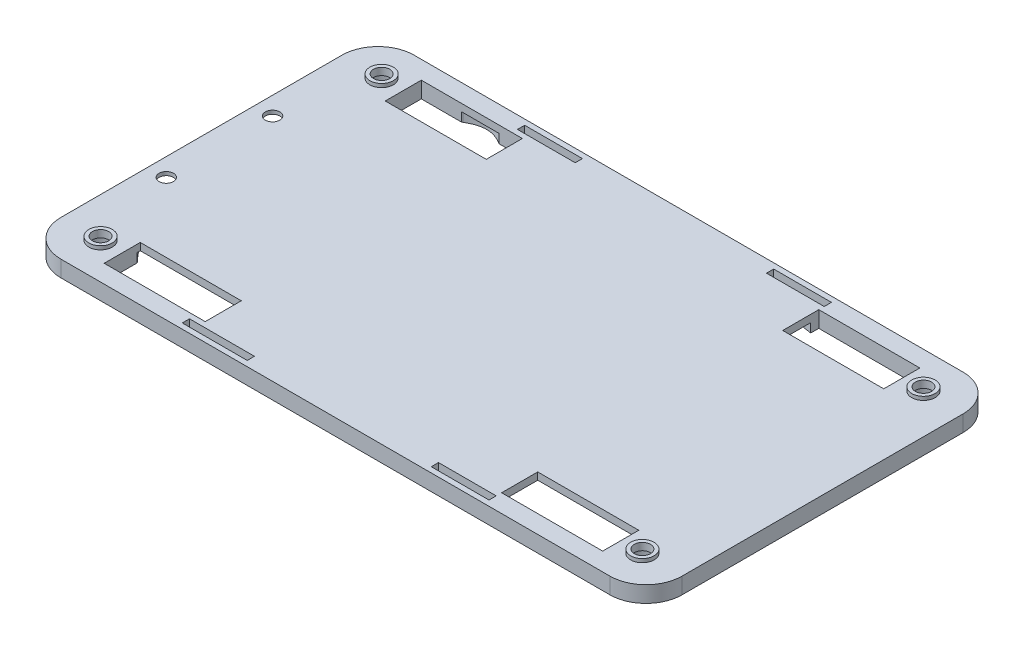
SolidWorks part; units mm, degrees
ref_plane "Front Plane" through (0, 0, 0) normal (0, 0, 1) x (1, 0, 0)
ref_plane "Top Plane" through (0, 0, 0) normal (0, 1, 0) x (1, 0, 0)
ref_plane "Right Plane" through (0, 0, 0) normal (1, 0, 0) x (0, 0, -1)
sketch "Sketch1" plane through (0, 0, 0) normal (0, 1, 0) x (1, 0, 0)
  line L1 (-78.1571, 35.933) -> (-78.1571, -14.1122)
  line L2 (78.9797, 0.0343) -> (-78.1571, 0.0343) construction
  line L3 (-77.1571, 35.7646) -> (-77.1571, -14.1122)
  line L4 (78.9797, -0.9657) -> (-78.1571, -0.9657)
  arc A1 (37.8695, -35.2975) -> (39.5975, -35.2134) centre (38.2635, -25.6055) ccw
  arc A2 (37.9263, -34.299) -> (39.4753, -34.2207) centre (38.2635, -25.6055) ccw
  spline S0 degree 1 poles (-77.1571, -14.1122) (-56.919, -31.9168) knots 0 0 1 1 construction
  spline S1 degree 1 poles (-56.919, -31.9168) (37.9263, -34.299) knots 0 0 1 1 construction
  spline S2 degree 1 poles (39.4753, -34.2207) (77.9849, 0.1477) knots 0 0 1 1 construction
  spline S3 degree 1 poles (77.9849, 0.1477) (25.0602, 52.8732) knots 0 0 1 1 construction
  spline S4 degree 1 poles (25.0602, 52.8732) (-5.6593, 44.1904) knots 0 0 1 1 construction
  spline S5 degree 1 poles (-5.6593, 44.1904) (-43.9853, 50.6886) knots 0 0 1 1 construction
  spline S6 degree 1 poles (-43.9853, 50.6886) (-59.7702, 54.7238) knots 0 0 1 1 construction
  spline S7 degree 1 poles (-59.7702, 54.7238) (-74.5158, 41.0521) knots 0 0 1 1 construction
  spline S8 degree 1 poles (-74.5158, 41.0521) (-77.1571, 35.7646) knots 0 0 1 1 construction
  spline S9 degree 3 poles (-77.1571, -14.1122) (-77.1565, -14.3701) (-77.1092, -14.8732) (-76.8359, -15.9559) (-76.1879, -17.5008) (-75.044, -19.4183) (-73.152, -22.0092) (-70.3495, -25.0822) (-66.8736, -28.0972) (-63.6864, -30.2141) (-61.0019, -31.4062) (-58.8274, -31.848) (-57.5718, -31.8794) (-56.919, -31.9168) knots 0.000484 0.000484 0.000484 0.000484 0.031521 0.062558 0.124632 0.186706 0.248781 0.372929 0.497077 0.621225 0.745373 0.869521 0.993669 0.993669 0.993669 0.993669
  spline S10 degree 3 poles (-56.919, -31.9168) (-56.6769, -31.8873) (-56.2021, -31.8274) (-55.1791, -31.687) (-53.8294, -31.4877) (-52.0759, -31.2184) (-49.5744, -30.8354) (-46.1465, -30.3372) (-41.5825, -29.7813) (-36.5976, -29.3261) (-29.4274, -28.913) (-19.5571, -28.8468) (-6.4839, -29.5875) (5.2448, -30.7865) (15.023, -31.9295) (22.521, -32.809) (30.1538, -33.642) (35.3408, -34.1075) (37.9263, -34.299) knots 0.000538 0.000538 0.000538 0.000538 0.016152 0.031766 0.062993 0.094221 0.125449 0.187904 0.250359 0.312815 0.37527 0.50018 0.625091 0.750001 0.812457 0.874912 0.937367 0.999822 0.999822 0.999822 0.999822
  spline S11 degree 3 poles (39.4753, -34.2207) (41.0079, -34.0574) (44.09, -33.7147) (50.0835, -32.8429) (57.0969, -31.1859) (64.2184, -27.8839) (69.7763, -23.1857) (73.0497, -18.2789) (74.9177, -14.0269) (75.9805, -10.7732) (76.7509, -7.5724) (77.1995, -5.064) (77.4798, -3.2279) (77.6607, -1.9649) (77.8261, -0.8108) (77.9301, -0.1834) (77.9849, 0.1477) knots -0.000309 -0.000309 -0.000309 -0.000309 0.063093 0.126495 0.253299 0.380104 0.506908 0.633712 0.697114 0.760516 0.823918 0.88732 0.919021 0.950722 0.982423 1.014124 1.014124 1.014124 1.014124
  spline S12 degree 3 poles (77.9849, 0.1477) (78.0286, 1.2633) (78.0637, 3.5224) (77.9426, 6.757) (77.6596, 9.9047) (77.0733, 13.9671) (75.9626, 18.7836) (73.4433, 25.9357) (69.0206, 33.8098) (62.0495, 41.4932) (53.7895, 47.3444) (44.6121, 51.2947) (34.9036, 53.2804) (28.3113, 53.2357) (25.0602, 52.8732) knots 0.000169 0.000169 0.000169 0.000169 0.031414 0.062658 0.093902 0.125147 0.187635 0.250124 0.375101 0.500079 0.625056 0.750034 0.875011 0.999988 0.999988 0.999988 0.999988
  spline S13 degree 3 poles (25.0602, 52.8732) (19.8954, 51.6294) (12.3224, 49.1317) (2.1607, 45.9713) (-3.0371, 44.6913) (-5.6593, 44.1904) knots 0.000659 0.000659 0.000659 0.000659 0.498067 0.746772 0.995476 0.995476 0.995476 0.995476
  spline S14 degree 3 poles (-5.6593, 44.1904) (-6.6879, 44.0461) (-8.7287, 43.7719) (-12.9633, 43.2668) (-18.1826, 42.7952) (-23.9015, 42.6322) (-28.8306, 42.9899) (-32.9666, 43.9514) (-35.9177, 45.2914) (-38.1959, 46.6779) (-39.9392, 47.8658) (-41.507, 48.9798) (-42.8638, 49.9292) (-43.6163, 50.4405) (-43.9853, 50.6886) knots -0.000196 -0.000196 -0.000196 -0.000196 0.062587 0.12537 0.250936 0.376501 0.502067 0.627632 0.753198 0.815981 0.878764 0.941546 0.972938 1.004329 1.004329 1.004329 1.004329
  spline S15 degree 3 poles (-43.9853, 50.6886) (-44.2445, 50.8673) (-44.7682, 51.2325) (-45.7507, 51.9331) (-46.8912, 52.7591) (-48.146, 53.6496) (-49.6971, 54.6811) (-51.4608, 55.6487) (-53.4077, 56.2593) (-55.2517, 56.3574) (-56.711, 56.0808) (-57.7948, 55.7138) (-58.5465, 55.3915) (-59.2299, 55.0428) (-59.5837, 54.8359) (-59.7702, 54.7238) knots -0.002497 -0.002497 -0.002497 -0.002497 0.029066 0.060629 0.123754 0.18688 0.250006 0.376257 0.502509 0.62876 0.755012 0.818137 0.881263 0.944389 1.007515 1.007515 1.007515 1.007515
  spline S16 degree 3 poles (-78.1571, -14.1122) (-78.1559, -14.7524) (-77.9173, -15.9777) (-77.0678, -17.9828) (-75.8538, -20.0098) (-73.8827, -22.6985) (-70.9901, -25.8584) (-67.4096, -28.9504) (-64.0991, -31.1349) (-61.2379, -32.3904) (-59.243, -32.7789) (-57.8421, -32.8756) (-57.2118, -32.9007) (-56.8882, -32.9203) knots 0.000409 0.000409 0.000409 0.000409 0.062843 0.125276 0.18771 0.250143 0.375011 0.499878 0.624745 0.749612 0.874479 0.936913 0.999346 0.999346 0.999346 0.999346
  spline S17 degree 3 poles (-56.8882, -32.9203) (-56.6427, -32.8908) (-56.1603, -32.8306) (-55.1309, -32.6904) (-53.7754, -32.491) (-52.0233, -32.2221) (-49.5292, -31.8398) (-46.1189, -31.3427) (-41.5829, -30.7872) (-36.6286, -30.3313) (-29.4997, -29.9158) (-19.6749, -29.8441) (-6.6369, -30.5782) (5.0856, -31.7749) (14.8757, -32.919) (22.3927, -33.8009) (30.0532, -34.6371) (35.2704, -35.1052) (37.8695, -35.2975) knots -0.001373 -0.001373 -0.001373 -0.001373 0.014273 0.029919 0.06121 0.092502 0.123794 0.186377 0.24896 0.311543 0.374127 0.499293 0.62446 0.749626 0.81221 0.874793 0.937376 0.99996 0.99996 0.99996 0.99996
  spline S18 degree 3 poles (39.5975, -35.2134) (41.1398, -35.049) (44.2356, -34.7045) (50.3018, -33.8209) (57.4502, -32.1301) (64.7991, -28.7164) (70.5782, -23.8111) (73.9656, -18.7006) (75.8832, -14.3057) (76.9672, -10.962) (77.7479, -7.6914) (78.1997, -5.145) (78.4804, -3.2966) (78.6613, -2.0308) (78.824, -0.9009) (78.9276, -0.2806) (78.9816, 0.0458) knots -0.000086 -0.000086 -0.000086 -0.000086 0.063428 0.126941 0.253967 0.380993 0.50802 0.635046 0.698559 0.762072 0.825585 0.889098 0.920855 0.952612 0.984368 1.016125 1.016125 1.016125 1.016125
  spline S19 degree 3 poles (78.9816, 0.0458) (79.0271, 1.1797) (79.0647, 3.4739) (78.9444, 6.7697) (78.6587, 9.9749) (78.0642, 14.1169) (76.9341, 19.0326) (74.3646, 26.3398) (69.8439, 34.3944) (62.712, 42.2543) (54.2626, 48.2351) (44.8799, 52.2671) (34.9529, 54.2886) (28.2109, 54.2351) (24.8869, 53.8601) knots -0.000407 -0.000407 -0.000407 -0.000407 0.03088 0.062166 0.093453 0.12474 0.187314 0.249888 0.375035 0.500183 0.62533 0.750478 0.875625 1.000773 1.000773 1.000773 1.000773
  spline S20 degree 3 poles (24.8869, 53.8601) (22.2839, 53.2349) (17.1223, 51.77) (6.9788, 48.4835) (-0.6206, 46.1711) (-5.8226, 45.1772) knots -0.001281 -0.001281 -0.001281 -0.001281 0.247714 0.49671 0.9947 0.9947 0.9947 0.9947
  spline S21 degree 3 poles (-5.8226, 45.1772) (-6.8463, 45.0337) (-8.8779, 44.761) (-13.0882, 44.2593) (-18.2643, 43.7927) (-23.9018, 43.6338) (-28.7026, 43.9859) (-32.6523, 44.9085) (-35.4477, 46.177) (-37.6484, 47.5152) (-39.3619, 48.6824) (-40.9248, 49.793) (-42.292, 50.7496) (-43.0505, 51.2651) (-43.4225, 51.5151) knots 0.000305 0.000305 0.000305 0.000305 0.063048 0.125791 0.251276 0.376761 0.502247 0.627732 0.753218 0.815961 0.878703 0.941446 0.972817 1.004189 1.004189 1.004189 1.004189
  spline S22 degree 3 poles (-43.4225, 51.5151) (-43.6786, 51.6918) (-44.1958, 52.0526) (-45.1684, 52.7462) (-46.308, 53.5714) (-47.577, 54.4721) (-49.1727, 55.5335) (-51.0441, 56.5648) (-53.2147, 57.2519) (-55.3195, 57.3652) (-56.9568, 57.0533) (-58.1477, 56.6506) (-58.9689, 56.2985) (-59.5708, 55.992) (-60.0059, 55.7483) (-60.1862, 55.6406) (-60.2803, 55.5839) knots -0.002294 -0.002294 -0.002294 -0.002294 0.029245 0.060783 0.12386 0.186936 0.250013 0.376167 0.50232 0.628473 0.754627 0.817704 0.88078 0.943857 0.975396 1.006934 1.006934 1.006934 1.006934
  spline S23 degree 3 poles (-60.2803, 55.5839) (-60.715, 55.3297) (-61.582, 54.801) (-63.2222, 53.7187) (-65.9105, 51.7373) (-69.2431, 48.741) (-72.0244, 45.6929) (-73.7392, 43.6279) (-74.6657, 42.4756) (-75.1049, 41.9202) (-75.3265, 41.639) knots 0.000427 0.000427 0.000427 0.000427 0.063268 0.126109 0.251792 0.503158 0.754524 0.880206 0.943048 1.005889 1.005889 1.005889 1.005889
  spline S24 degree 3 poles (-59.7702, 54.7238) (-60.1936, 54.4761) (-61.0386, 53.9612) (-62.6368, 52.9072) (-65.2587, 50.9763) (-68.5171, 48.0498) (-71.2443, 45.0657) (-73.1899, 42.7247) (-74.0698, 41.6179) (-74.5158, 41.0521) knots 0.000174 0.000174 0.000174 0.000174 0.062881 0.125589 0.251004 0.501833 0.752662 0.878077 1.003492 1.003492 1.003492 1.003492
  spline S25 degree 3 poles (-74.5158, 41.0521) (-75.0658, 40.2217) (-76.0765, 38.4779) (-76.8336, 36.6875) (-77.1571, 35.7646) knots 0.499549 0.499549 0.499549 0.499549 0.499766 0.499983 0.499983 0.499983 0.499983
  spline S26 degree 3 poles (-75.3265, 41.639) (-75.92, 40.746) (-77.0064, 38.8701) (-77.815, 36.9314) (-78.1571, 35.933) knots 0.499546 0.499546 0.499546 0.499546 0.49977 0.499995 0.499995 0.499995 0.499995
  point P0 (0.4631, 0.0343)
  dimension "D1" = 1
sketch "Sketch6" plane through (0, 0, 0) normal (0, 1, 0) x (1, 0, 0)
  line L0 (-78.1571, 35.933) -> (-78.1571, -14.1122) construction
  line L1 (73.9816, 59.5839) -> (-78.1571, 59.5839)
  line L2 (83.9816, 49.5839) -> (83.9816, -28.2975)
  line L3 (73.9816, -38.2975) -> (-78.1571, -38.2975)
  line L4 (-88.1571, 49.5839) -> (-88.1571, -28.2975)
  arc A0 (-78.1571, -38.2975) -> (-88.1571, -28.2975) centre (-78.1571, -28.2975) cw
  arc A1 (-88.1571, 49.5839) -> (-78.1571, 59.5839) centre (-78.1571, 49.5839) cw
  arc A2 (73.9816, 59.5839) -> (83.9816, 49.5839) centre (73.9816, 49.5839) cw
  arc A3 (83.9816, -28.2975) -> (73.9816, -38.2975) centre (73.9816, -28.2975) cw
  dimension "D5" = 10
  dimension "D1" = 5
  dimension "D2" = 10
  dimension "D3" = 3
  dimension "D4" = 4
extrude "Boss-Extrude2" add sketch "Sketch6" along normal blind 5.5
extrude "Cut-Extrude1" cut sketch "Sketch1" along normal blind 2.5 contours A2 S11 L4 L3 S9 S10 | S24 S25 L3 L4 S11 S12 S13 S14 S15 region at (0.1139, 0, 15.5782) region at (-2.2602, 0, -23.2786)
sketch "Sketch7" plane through (0, 0, 0) normal (0, -1, 0) x (1, 0, 0)
  line L1 (-76.2189, 14.1122) -> (-91.3452, 14.1122)
  line L2 (-76.2189, 14.1122) -> (-76.2189, -35.933)
  line L3 (-76.2189, -35.933) -> (-91.3452, -35.933)
  line L4 (-91.3452, 14.1122) -> (-91.3452, -35.933)
extrude "Cut-Extrude2" cut sketch "Sketch7" against normal up to surface (2.5 mm away) contours L2 L1 L4 L3 up to face at (-19.4492, 2.5, -12.7234)
sketch "Sketch8" plane through (0, 5.5, 0) normal (0, 1, 0) x (1, 0, 0)
  line L0 (83.9816, 10.6432) -> (-88.1571, 10.6432) construction
  line L1 (83.9816, -28.2975) -> (83.9816, 49.5839) construction
  line L2 (-88.1571, 49.5839) -> (-88.1571, -28.2975) construction
  line L3 (-2.0877, 59.5839) -> (-2.0877, -38.2975) construction
  line L4 (73.9816, 59.5839) -> (-78.1571, 59.5839) construction
  line L5 (-78.1571, -38.2975) -> (73.9816, -38.2975) construction
  line L7 (78.9816, 54.5839) -> (38.9816, 54.5839)
  line L8 (78.9816, 54.5839) -> (78.9816, 44.5839)
  line L9 (78.9816, 44.5839) -> (38.9816, 44.5839)
  line L10 (38.9816, 54.5839) -> (38.9816, 44.5839)
  line L22 (38.9816, 49.5839) -> (78.9816, 49.5839) construction
  line L23 (66.9816, 54.5839) -> (66.9816, 44.5839)
  circle A1 centre (72.9816, 49.5839) radius 3.5
  dimension "D6" = 7
  dimension "D1" = 10
  dimension "D2" = 40
  dimension "D3" = 5
  dimension "D4" = 5
  dimension "D5" = 6
  dimension "D7" = 6
sketch "Sketch9" plane through (0, 0, 0) normal (0, -1, 0) x (1, 0, 0)
  circle A0 centre (72.9816, -49.5839) radius 4.5
  dimension "D1" = 9
extrude "Cut-Extrude5" cut sketch "Sketch9" against normal blind 3.5
sketch "Sketch10" plane through (0, 3.5, 0) normal (0, -1, 0) x (1, 0, 0)
  circle A0 centre (72.9816, -49.5839) radius 2.25
  dimension "D1" = 4.5
extrude "Cut-Extrude6" cut sketch "Sketch10" against normal blind 21
extrude "Cut-Extrude8" cut sketch "Sketch8" against normal blind 42 contours L23 L7 L10 L9 region at (52.9816, 5.5, -49.5839)
extrude "Cut-Extrude9" cut sketch "Sketch8<3>" against normal blind 1 contours L7 L23 L9 L8 A1 region at (78.8254, 5.5, -49.5839)
sketch "Sketch8<3>" plane through (0, 5.5, 0) normal (0, 1, 0) x (1, 0, 0) same geometry as "Sketch8"
sketch "Sketch12" plane through (0, 5.5, 0) normal (0, 1, 0) x (1, 0, 0)
  line L0 (-88.1571, 10.6432) -> (83.9816, 10.6432) construction
  line L1 (-88.1571, 49.5839) -> (-88.1571, -28.2975) construction
  line L2 (83.9816, -28.2975) -> (83.9816, 49.5839) construction
  line L3 (-2.0877, 59.5839) -> (-2.0877, -36.8461) construction
  line L4 (73.9816, 59.5839) -> (-78.1571, 59.5839) construction
ref_plane "Plane1" through (0, 0, -10.6432) normal (0, 0, 1) x (1, 0, 0)
ref_plane "Plane2" through (-2.0877, 0, 0) normal (-1, 0, 0) x (0, 0, 1)
mirror "Mirror1" about plane through (0, 0, -10.6432) normal (0, 0, 1) of "Cut-Extrude5", "Cut-Extrude6", "Cut-Extrude8", "Cut-Extrude9"
mirror "Mirror2" about plane through (-2.0877, 0, 0) normal (-1, 0, 0) of "Mirror1", "Cut-Extrude9", "Cut-Extrude8", "Cut-Extrude6", "Cut-Extrude5"
sketch "Sketch13" plane through (0, 5.5, 0) normal (0, 1, 0) x (1, 0, 0)
  line L0 (-83.1571, 44.5839) -> (-43.1571, 44.5839) construction
  line L1 (58.9816, 39.5839) -> (-63.1571, 39.5839)
  line L2 (58.9816, 39.5839) -> (58.9816, -18.2975)
  line L3 (58.9816, -18.2975) -> (-63.1571, -18.2975)
  line L4 (-63.1571, 39.5839) -> (-63.1571, -18.2975)
  line L5 (58.9816, 39.5839) -> (-63.1571, -18.2975) construction
  line L6 (58.9816, -18.2975) -> (-63.1571, 39.5839) construction
  line L7 (-83.1571, -23.2975) -> (-43.1571, -23.2975) construction
  line L8 (83.9816, -28.2975) -> (83.9816, 49.5839) construction
  line L9 (-88.1571, 49.5839) -> (-88.1571, -28.2975) construction
  point P0 (-2.0877, 10.6432)
  dimension "D1" = 5
  dimension "D2" = 5
  dimension "D3" = 25
  dimension "D4" = 25
extrude "Cut-Extrude10" cut sketch "Sketch13" against normal blind 1
sketch "Sketch16" plane through (0, 0, 0) normal (0, -1, 0) x (1, 0, 0)
  line L0 (78.9816, -0.5458) -> (78.9816, -79.1994) construction
  line L1 (22.9816, -56.0839) -> (-37.6427, -56.0839) construction
  line L2 (73.9816, -59.5839) -> (-78.1571, -59.5839) construction
  line L3 (38.9816, -54.3238) -> (38.9816, 38.2975) construction
  line L4 (38.9816, -59.5839) -> (38.9816, -54.3238) construction
  line L5 (38.9816, -56.0839) -> (22.9816, -56.0839)
  line L6 (38.9816, -56.0839) -> (38.9816, -58.0839)
  line L7 (38.9816, -58.0839) -> (22.9816, -58.0839)
  line L8 (22.9816, -56.0839) -> (22.9816, -58.0839)
  line L9 (-78.1571, 38.2975) -> (73.9816, 38.2975) construction
  line L10 (22.9816, -56.0839) -> (22.9816, 38.2975) construction
  line L12 (38.9816, 36.7975) -> (22.9816, 36.7975)
  line L13 (38.9816, 36.7975) -> (38.9816, 34.7975)
  line L14 (38.9816, 34.7975) -> (22.9816, 34.7975)
  line L15 (22.9816, 36.7975) -> (22.9816, 34.7975)
  line L16 (22.9816, 34.7975) -> (-46.0184, 34.7975) construction
  line L17 (-30.0184, -56.0839) -> (-46.0184, -56.0839)
  line L18 (-30.0184, -56.0839) -> (-30.0184, -58.0839)
  line L19 (-30.0184, -58.0839) -> (-46.0184, -58.0839)
  line L20 (-46.0184, -56.0839) -> (-46.0184, -58.0839)
  line L22 (-28.0184, 34.7975) -> (-46.0184, 34.7975)
  line L23 (-28.0184, 34.7975) -> (-28.0184, 36.7975)
  line L24 (-28.0184, 36.7975) -> (-46.0184, 36.7975)
  line L25 (-46.0184, 34.7975) -> (-46.0184, 36.7975)
  dimension "D1" = 40
  dimension "D2" = 16
  dimension "D3" = 1.5
  dimension "D4" = 2
  dimension "D5" = 2
  dimension "D6" = 1.5
  dimension "D7" = 125
  dimension "D8" = 16
  dimension "D9" = 2
  dimension "D10" = 18
  dimension "D11" = 2
extrude "Cut-Extrude12" cut sketch "Sketch16" against normal blind 57
sketch "Sketch17" plane through (0, 4.5, 0) normal (0, 1, 0) x (1, 0, 0)
  line L1 (-99.5963, 69.0247) -> (98.4238, 69.0247)
  line L2 (-99.5963, 69.0247) -> (-99.5963, -53.2143)
  line L3 (-99.5963, -53.2143) -> (98.4238, -53.2143)
  line L4 (98.4238, 69.0247) -> (98.4238, -53.2143)
extrude "Cut-Extrude14" cut sketch "Sketch17" along normal blind 48.5
sketch "Sketch23" plane through (0, 2.5, 0) normal (0, -1, 0) x (1, 0, 0)
  line L0 (-88.1571, -10.9104) -> (-64.7808, -10.9104) construction
  line L1 (-88.1571, -35.933) -> (-88.1571, 14.1122) construction
  circle A0 centre (-83.1571, 4.0896) radius 2
  circle A1 centre (-83.1571, 4.0896) radius 4.25
  dimension "D1" = 4
  dimension "D4" = 8.5
  dimension "D2" = 15
  dimension "D3" = 5
extrude "Cut-Extrude15" cut sketch "Sketch23" against normal blind 48.5 contours A0
extrude "Cut-Extrude16" cut sketch "Sketch23<3>" against normal blind 1
sketch "Sketch23<3>" plane through (0, 2.5, 0) normal (0, -1, 0) x (1, 0, 0) same geometry as "Sketch23"
mirror "Mirror4" about plane through (0, 0, -10.6432) normal (0, 0, 1) of "Cut-Extrude16", "Cut-Extrude15"
sketch "Sketch24" plane through (0, 4.5, 0) normal (0, 1, 0) x (1, 0, 0)
  circle A0 centre (-77.1571, 49.5839) radius 3.25
  circle A1 centre (-77.1571, 49.5839) radius 2.25
  circle A2 centre (72.9816, 49.5839) radius 2.25
  circle A3 centre (72.9816, 49.5839) radius 3.25
  circle A4 centre (72.9816, -28.2975) radius 2.25
  circle A5 centre (-77.1571, -28.2975) radius 2.25
  circle A6 centre (-77.1571, -28.2975) radius 3.25
  circle A7 centre (72.9816, -28.2975) radius 3.25
  dimension "D1" = 6.5
  dimension "D2" = 6.5
  dimension "D3" = 6.5
  dimension "D4" = 6.5
extrude "Boss-Extrude3" add sketch "Sketch24" along normal blind 1
